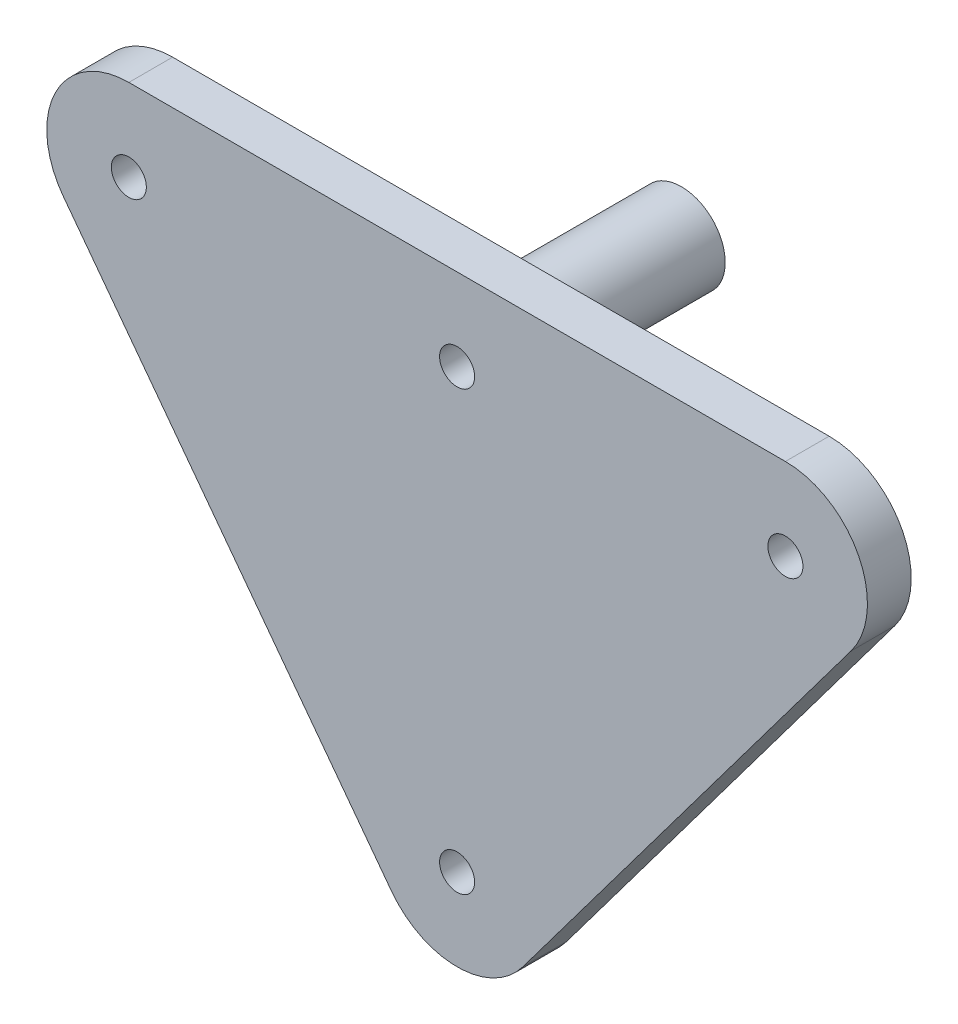
SolidWorks part; units mm, degrees
ref_plane "Front Plane" through (0, 0, 0) normal (0, 0, 1) x (1, 0, 0)
ref_plane "Top Plane" through (0, 0, 0) normal (0, 1, 0) x (1, 0, 0)
ref_plane "Right Plane" through (0, 0, 0) normal (1, 0, 0) x (0, 0, -1)
ref_axis "X" through (-88.99, 0, 0) along (1, 0, 0)
ref_axis "Y" through (0, 55, 0) along (0, -1, 0)
ref_axis "Z" through (0, 0, -88.99) along (0, 0, 1)
sketch "Sketch1" plane through (0, 0, 0) normal (0, 0, 1) x (1, 0, 0)
  line L0 (-36, 15.5) -> (-6, -24.5)
  line L1 (6, -24.5) -> (36, 15.5)
  line L2 (-30, 27.5) -> (30, 27.5)
  circle A0 centre (-30, 20) radius 7.5
  circle A1 centre (30, 20) radius 7.5
  circle A2 centre (0, -20) radius 7.5
  circle A3 centre (0, 20) radius 7.5
  circle A4 centre (0, 20) radius 4
  circle A5 centre (0, -20) radius 4
  circle A6 centre (-30, 20) radius 1.6
  circle A7 centre (0, 20) radius 1.6
  circle A8 centre (0, -20) radius 1.6
  circle A9 centre (30, 20) radius 1.6
  dimension "D1" = 15
  dimension "D2" = 8
  dimension "D3" = 3.2
extrude "Boss-Extrude1" add sketch "Sketch1" along normal blind 4 contours A0 | L2 A3 A0 L0 A2 L1 A1 | A1 | A2 A5 | A3 A4 | A4 | A5 region at (5.1533, 25.1533, 0) region at (0, 6.0857, 0) region at (-36.5185, 23.2592, 0) region at (-2.3046, -13.0861, 0) region at (23.4815, 16.7408, 0) region at (-3.8869, 20, 0) region at (-3.8869, -20, 0)
extrude "Boss-Extrude2" add sketch "Sketch1<4>" against normal up to surface (16.5 mm away) contours A4 A7 | A5 A8 region at (-3.8869, 20, 0) region at (-3.8869, -20, 0)
sketch "Sketch1<4>" plane through (0, 0, 0) normal (0, 0, 1) x (1, 0, 0) same geometry as "Sketch1"
fillet "Fillet1" radius 2 2 edges at (4, -20, 0) (4, 20, 0)
